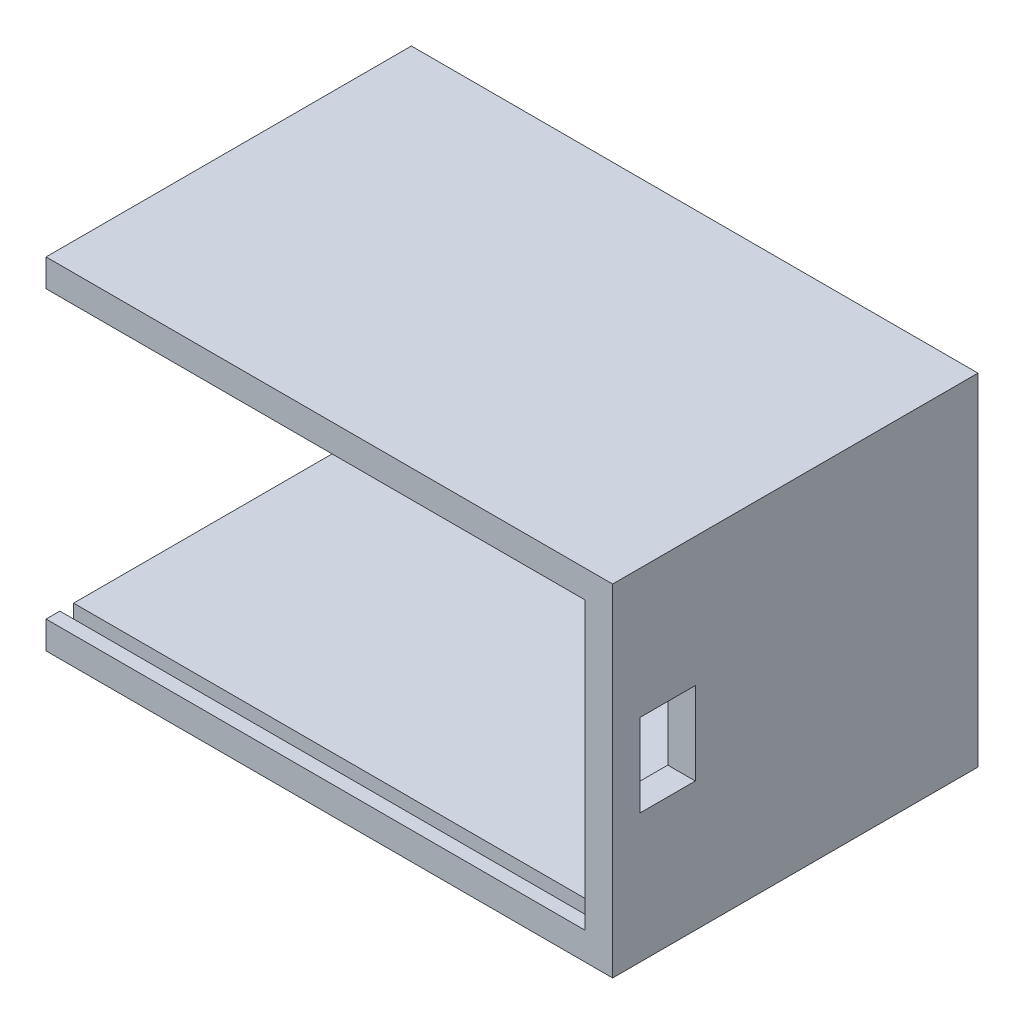
SolidWorks part; units mm, degrees
ref_plane "Plan de face" through (0, 0, 0) normal (0, 0, 1) x (1, 0, 0)
ref_plane "Plan de dessus" through (0, 0, 0) normal (0, 1, 0) x (1, 0, 0)
ref_plane "Plan de droite" through (0, 0, 0) normal (1, 0, 0) x (0, 0, -1)
sketch "Esquisse1" plane through (0, 0, 0) normal (0, 0, 1) x (1, 0, 0)
  line L1 (-41.1, 24.75) -> (41.1, 24.75)
  line L2 (-41.1, 24.75) -> (-41.1, -24.75)
  line L3 (-41.1, -24.75) -> (41.1, -24.75)
  line L4 (41.1, 24.75) -> (41.1, -24.75)
  line L5 (-41.1, 24.75) -> (41.1, -24.75) construction
  line L6 (-41.1, -24.75) -> (41.1, 24.75) construction
  point P0 (0, 0)
  dimension "D1" = 82.2
  dimension "D2" = 49.5
extrude "Boss.-Extru.1" add sketch "Esquisse1" along normal blind 3
sketch "Esquisse2" plane through (0, 0, 3) normal (0, 0, 1) x (1, 0, 0)
  line L0 (41.1, 24.75) -> (-41.1, 24.75) construction
  line L1 (-37.1, 20.75) -> (37.1, 20.75)
  line L2 (-37.1, 20.75) -> (-37.1, -20.75)
  line L3 (-37.1, -20.75) -> (37.1, -20.75)
  line L4 (37.1, 20.75) -> (37.1, -20.75)
  line L5 (-37.1, 20.75) -> (37.1, -20.75) construction
  line L6 (-37.1, -20.75) -> (37.1, 20.75) construction
  line L8 (-41.1, 24.75) -> (41.1, 24.75)
  line L9 (-41.1, 24.75) -> (-41.1, -24.75) construction
  line L10 (-41.1, 24.75) -> (-41.1, -24.75)
  line L11 (-41.1, -24.75) -> (41.1, -24.75)
  line L12 (41.1, 24.75) -> (41.1, -24.75)
  line L13 (-41.1, 24.75) -> (41.1, -24.75) construction
  line L14 (-41.1, -24.75) -> (41.1, 24.75) construction
  point P0 (0, 0)
  point P10 (0, 0)
  dimension "D1" = 4
  dimension "D2" = 4
extrude "Boss.-Extru.2" add sketch "Esquisse2" along normal blind 50
sketch "Esquisse4" plane through (-37.1, 0, 0) normal (1, 0, 0) x (0, 0, -1)
  line L1 (-53, 20.75) -> (-51, 20.75)
  line L2 (-53, 20.75) -> (-53, -20.75)
  line L3 (-53, -20.75) -> (-51, -20.75)
  line L4 (-51, 20.75) -> (-51, -20.75)
  dimension "D1" = 2
extrude "Enlèv. mat.-Extru.3" cut sketch "Esquisse4" against normal blind 16
sketch "Esquisse5" plane through (-41.1, 0, 0) normal (-1, 0, 0) x (0, 0, 1)
  line L0 (51, 22.75) -> (49, 22.75)
  line L1 (49, 22.75) -> (49, -22.75)
  line L2 (49, -22.75) -> (51, -22.75)
  line L3 (51, -22.75) -> (51, -20.75)
  line L4 (51, 22.75) -> (51, 20.75)
  line L5 (51, 20.75) -> (51, -20.75)
  dimension "D1" = 2
  dimension "D2" = 2
  dimension "D3" = 2
extrude "Enlèv. mat.-Extru.4" cut sketch "Esquisse5" against normal blind 80.2
sketch "Esquisse6" plane through (-37.1, 0, 0) normal (1, 0, 0) x (0, 0, -1)
  line L1 (-3, 20.75) -> (-49, 20.75)
  line L2 (-3, 20.75) -> (-3, -20.75)
  line L3 (-3, -20.75) -> (-49, -20.75)
  line L4 (-49, 20.75) -> (-49, -20.75)
extrude "Enlèv. mat.-Extru.5" cut sketch "Esquisse6" against normal blind 10
sketch "Esquisse7" plane through (37.1, 0, 0) normal (-1, 0, 0) x (0, 0, 1)
  line L0 (0, 24.75) -> (0, -24.75) construction
  line L1 (13, 4.5) -> (18, 4.5)
  line L2 (13, 4.5) -> (13, -4.5)
  line L3 (13, -4.5) -> (18, -4.5)
  line L4 (18, 4.5) -> (18, -4.5)
  dimension "D1" = 9
  dimension "D2" = 5
  dimension "D3" = 13
  dimension "D4" = 4.5
extrude "Boss.-Extru.3" add sketch "Esquisse7" along normal blind 20
chamfer "Chanfrein1" distance 5 angle 45 1 edges at (37.1, 0, 18)
chamfer "Chanfrein2" distance 2 angle 45 1 edges at (37.1, 0, 13)
chamfer "Chanfrein3" distance 2 angle 45 2 edges at (37.1, -4.5, 17) (37.1, 4.5, 17)
sketch "Esquisse8" plane through (0, 0, 0) normal (0, 0, -1) x (-1, 0, 0)
  line L1 (-37.1, -20.75) -> (-37.1, 20.75) construction
  circle A0 centre (-23.6, 0) radius 6.75
  dimension "D1" = 13.5
  dimension "D2" = 13.5
  dimension "D3" = 0
extrude "Enlèv. mat.-Extru.6" cut sketch "Esquisse8" against normal blind 5
sketch "Esquisse9" plane through (0, 0, 0) normal (0, 0, -1) x (-1, 0, 0)
  line L1 (-3.6, -6.1) -> (29.4, -6.1)
  line L2 (-3.6, -6.1) -> (-3.6, 6.1)
  line L3 (-3.6, 6.1) -> (29.4, 6.1)
  line L4 (29.4, -6.1) -> (29.4, 6.1)
  circle A0 centre (-23.6, 0) radius 6.75 construction
  point P4 (-3.6, 0)
  dimension "D1" = 12.2
  dimension "D2" = 33
  dimension "D3" = 0
  dimension "D4" = 20
sketch "Esquisse10" plane through (0, 0, 3) normal (0, 0, 1) x (1, 0, 0)
  line L0 (3.6, -6.1) -> (-29.4, -6.1) construction
  line L1 (-20.9, 8.5) -> (6, 8.5)
  line L2 (-20.9, 8.5) -> (-20.9, -8.5)
  line L3 (-20.9, -8.5) -> (6, -8.5)
  line L4 (6, 8.5) -> (6, -8.5)
  line L5 (-20.9, 8.5) -> (6, -8.5) construction
  line L6 (-20.9, -8.5) -> (6, 8.5) construction
  line L10 (3.6, -6.1) -> (3.6, 6.1) construction
  line L11 (-29.4, -6.1) -> (-29.4, 6.1) construction
  point P0 (-7.45, 0)
  dimension "D1" = 6.1
  dimension "D2" = 2.4
  dimension "D3" = 17
  dimension "D4" = 8.5
extrude "Boss.-Extru.4" add sketch "Esquisse10" along normal blind 4.5
extrude "Enlèv. mat.-Extru.8" cut sketch "Esquisse9" against normal blind 5
sketch "Esquisse11" plane through (-29.4, 0, 0) normal (1, 0, 0) x (0, 0, -1)
  line L0 (-3, -6.1) -> (0, -6.1) construction
  line L1 (-3, 6.1) -> (-0.8, 6.1)
  line L2 (-3, 6.1) -> (-3, -6.1)
  line L3 (-3, -6.1) -> (-0.8, -6.1)
  line L4 (-0.8, 6.1) -> (-0.8, -6.1)
  dimension "D1" = 0.8
extrude "Enlèv. mat.-Extru.9" cut sketch "Esquisse11" against normal blind 7
sketch "Esquisse12" plane through (0, 0, 0) normal (0, 0, -1) x (-1, 0, 0)
  line L1 (35.1, -20.75) -> (17.1, -20.75)
  line L2 (35.1, -20.75) -> (35.1, -9.75)
  line L3 (35.1, -9.75) -> (17.1, -9.75)
  line L4 (17.1, -20.75) -> (17.1, -9.75)
  line L5 (41.1, 24.75) -> (41.1, -24.75) construction
  line L6 (41.1, -20.75) -> (-37.1, -20.75) construction
  dimension "D1" = 0
  dimension "D2" = 6
  dimension "D3" = 11
  dimension "D4" = 18
extrude "Enlèv. mat.-Extru.10" cut sketch "Esquisse12" against normal blind 2
sketch "Esquisse13" plane through (0, 0, 2) normal (0, 0, -1) x (-1, 0, 0)
  line L0 (35.1, -9.75) -> (17.1, -9.75) construction
  line L1 (19.6, -9.75) -> (32.6, -9.75)
  line L2 (19.6, -9.75) -> (19.6, -20.75)
  line L3 (19.6, -20.75) -> (32.6, -20.75)
  line L4 (32.6, -9.75) -> (32.6, -20.75)
  line L5 (17.1, -20.75) -> (35.1, -20.75) construction
  line L6 (35.1, -20.75) -> (35.1, -9.75) construction
  line L8 (19.6, -9.75) -> (24.1, -9.75)
  line L9 (19.6, -9.75) -> (19.6, -20.75)
  line L10 (19.6, -20.75) -> (24.1, -20.75)
  line L11 (24.1, -9.75) -> (24.1, -20.75)
  line L12 (32.6, -9.75) -> (28.1, -9.75)
  line L13 (32.6, -9.75) -> (32.6, -20.75)
  line L14 (32.6, -20.75) -> (28.1, -20.75)
  line L15 (28.1, -9.75) -> (28.1, -20.75)
  dimension "D1" = 13
  dimension "D2" = 2.5
  dimension "D3" = 4.5
  dimension "D4" = 4.5
extrude "Enlèv. mat.-Extru.11" cut sketch "Esquisse13" against normal blind 3 contours L9 L8 L11 L10 | L13 L12 L15 L14
sketch "Esquisse14" plane through (0, 0, 3) normal (0, 0, 1) x (1, 0, 0)
  line L1 (-28.1, -9.75) -> (-24.1, -9.75)
  line L2 (-28.1, -9.75) -> (-28.1, -20.75)
  line L3 (-28.1, -20.75) -> (-24.1, -20.75)
  line L4 (-24.1, -9.75) -> (-24.1, -20.75)
extrude "Boss.-Extru.5" add sketch "Esquisse14" along normal blind 3
sketch "Esquisse15" plane through (0, 0, 2) normal (0, 0, -1) x (-1, 0, 0)
  line L1 (24.1, -9.75) -> (28.1, -9.75)
  line L2 (24.1, -9.75) -> (24.1, -20.75)
  line L3 (24.1, -20.75) -> (28.1, -20.75)
  line L4 (28.1, -9.75) -> (28.1, -20.75)
extrude "Enlèv. mat.-Extru.12" cut sketch "Esquisse15" against normal blind 3
sketch "Esquisse16" plane through (0, 0, 3) normal (0, 0, 1) x (1, 0, 0)
  line L1 (-28.1, -9.75) -> (-21.1, -9.75)
  line L2 (-28.1, -9.75) -> (-28.1, -8.25)
  line L3 (-28.1, -8.25) -> (-21.1, -8.25)
  line L4 (-21.1, -9.75) -> (-21.1, -8.25)
  dimension "D1" = 7
  dimension "D2" = 1.5
extrude "Boss.-Extru.6" add sketch "Esquisse16" along normal blind 3
chamfer "Chanfrein4" distance 3 angle 45 1 edges at (6, 0, 3)
sketch "Esquisse18" plane through (0, 0, 3) normal (0, 0, 1) x (1, 0, 0)
  line L0 (-19.6, -9.75) -> (-21.1, -9.75) construction
  line L1 (-21.1, -8.25) -> (-20.9, -8.25)
  line L2 (-21.1, -8.25) -> (-21.1, -9.75)
  line L3 (-21.1, -9.75) -> (-20.9, -9.75)
  line L4 (-20.9, -8.25) -> (-20.9, -9.75)
  line L6 (-28.1, -9.75) -> (-32.6, -9.75)
  line L7 (-28.1, -9.75) -> (-28.1, -8.25)
  line L8 (-28.1, -8.25) -> (-32.6, -8.25)
  line L9 (-32.6, -9.75) -> (-32.6, -8.25)
extrude "Boss.-Extru.8" add sketch "Esquisse18" along normal up to surface (3 mm away)
sketch "Esquisse19" plane through (-20.9, 0, 0) normal (1, 0, 0) x (0, 0, -1)
  line L1 (-6, -8.5) -> (-3, -8.5)
  line L2 (-6, -8.5) -> (-6, -9.75)
  line L3 (-6, -9.75) -> (-3, -9.75)
  line L4 (-3, -8.5) -> (-3, -9.75)
extrude "Boss.-Extru.9" add sketch "Esquisse19" along normal blind 3
sketch "Esquisse20" plane through (0, -9.75, 0) normal (0, -1, 0) x (-1, 0, 0)
  line L0 (17.9, -6) -> (17.9, -3) construction
  line L1 (24.1, -6) -> (17.9, -6)
  line L2 (24.1, -6) -> (24.1, -5)
  line L3 (24.1, -5) -> (17.9, -5)
  line L4 (17.9, -6) -> (17.9, -5)
  line L6 (19.6, -3) -> (17.9, -3)
  line L7 (19.6, -3) -> (19.6, -5)
  line L8 (19.6, -5) -> (17.9, -5)
  line L9 (17.9, -3) -> (17.9, -5)
  dimension "D1" = 2
extrude "Boss.-Extru.10" add sketch "Esquisse20" along normal up to surface (11 mm away) contours L2 L1 L4 L3 | L7 L6 L9 L8 up to face at (-2, -20.75, 52)
chamfer "Chanfrein10" distance 5 angle 33 1 edges at (-17.9, -14.625, 3) first distance on face at (-16.4706, -3.9853, 3)
chamfer "Chanfrein11" distance 2 angle 45 1 edges at (-20.9, -8.25, 4.5)
sketch "Esquisse21" plane through (41.1, 0, 0) normal (1, 0, 0) x (0, 0, -1)
  line L0 (-53, -24.75) -> (-53, 24.75) construction
  line L1 (-49, 6) -> (-41, 6)
  line L2 (-49, 6) -> (-49, -6)
  line L3 (-49, -6) -> (-41, -6)
  line L4 (-41, 6) -> (-41, -6)
  line L5 (-49, 20.75) -> (-49, -20.75) construction
  point P6 (-41, 0)
  point P7 (-53, 0)
  dimension "D1" = 8
  dimension "D2" = 12
  dimension "D3" = 0
  dimension "D4" = 0
extrude "Enlèv. mat.-Extru.13" cut sketch "Esquisse21" against normal blind 10
